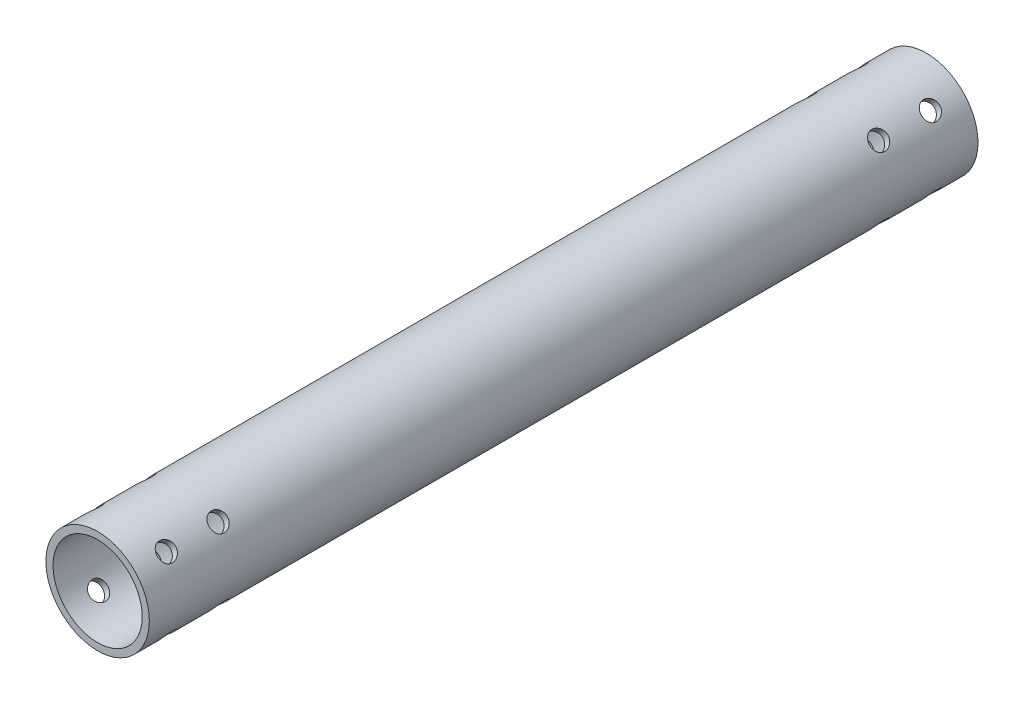
SolidWorks part; units mm, degrees
ref_plane "Front Plane" through (0, 0, 0) normal (0, 0, 1) x (1, 0, 0)
ref_plane "Top Plane" through (0, 0, 0) normal (0, 1, 0) x (1, 0, 0)
ref_plane "Right Plane" through (0, 0, 0) normal (1, 0, 0) x (0, 0, -1)
sketch "Sketch1" plane through (0, 0, 0) normal (0, 0, 1) x (1, 0, 0)
  circle A0 centre (0, 0) radius 8
  circle A1 centre (0, 0) radius 6.9
  dimension "D1" = 16
  dimension "D2" = 13.8
extrude "Boss-Extrude1" add sketch "Sketch1" along normal blind 128.2
sketch "Sketch2" plane through (0, 0, 0) normal (0, 1, 0) x (1, 0, 0)
  line L0 (-8, -128.2) -> (8, -128.2) construction
  circle A1 centre (0, -128.2) radius 2.5
extrude "Boss-Extrude2" [suppressed] add sketch "Sketch2" along normal blind 8 and the other way blind 8
ref_axis "Axis1" through (0, 0, -6.41) along (0, 0, 1)
ref_plane "Plane1" through (0, 0, 0) normal (-0.7071, 0.7071, 0) x (0, 0, 1)
sketch "Sketch3" plane through (0, 0, 0) normal (-0.7071, 0.7071, 0) x (0, 0, 1)
  circle A0 centre (115.2, 0) radius 1.4 construction
  circle A1 centre (123.2, 0) radius 1.4 construction
  circle A2 centre (115.2, 0) radius 1.4
  circle A3 centre (123.2, 0) radius 1.4
  circle A4 centre (13, 0) radius 1.4 construction
  circle A5 centre (5, 0) radius 1.4 construction
  circle A6 centre (13, 0) radius 1.4
  circle A7 centre (5, 0) radius 1.4
extrude "Cut-Extrude1" cut sketch "Sketch3" against normal through all and the other way through all
pattern_circular "CirPattern1" count 2 over 90 about axis through (0, 0, -6.41) along (0, 0, 1) of "Cut-Extrude1"
